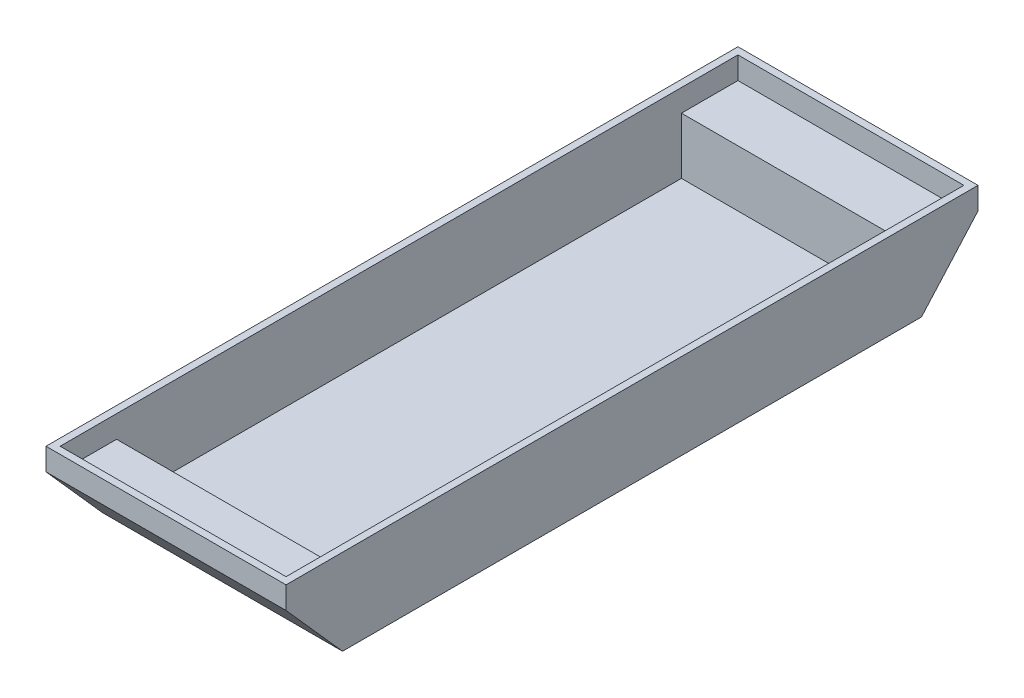
SolidWorks part; units mm, degrees
material "ABS PC"
ref_plane "Front Plane" through (0, 0, 0) normal (0, 0, 1) x (1, 0, 0)
ref_plane "Top Plane" through (0, 0, 0) normal (0, 1, 0) x (1, 0, 0)
ref_plane "Right Plane" through (0, 0, 0) normal (1, 0, 0) x (0, 0, -1)
sketch "Sketch3" plane through (0, 0, 0) normal (1, 0, 0) x (0, 0, -1)
  line L29 (108.2745, 46.8041) -> (95.5745, 32.5166)
  line L30 (108.2745, 46.8041) -> (95.5745, 46.8041)
  line L31 (-47.3005, 46.8041) -> (-34.6005, 32.5166)
  line L32 (-47.3005, 46.8041) -> (-34.6005, 46.8041)
  line L95 (95.5745, 32.5166) -> (95.5745, 46.8041)
  line L96 (68.587, 32.5166) -> (95.5745, 32.5166)
  line L97 (43.187, 32.5166) -> (68.587, 32.5166)
  line L98 (17.787, 32.5166) -> (43.187, 32.5166)
  line L99 (-7.613, 32.5166) -> (17.787, 32.5166)
  line L100 (-34.6005, 32.5166) -> (-7.613, 32.5166)
  line L101 (-34.6005, 46.8041) -> (-34.6005, 32.5166)
  line L102 (95.5745, 32.5166) -> (95.5745, 46.8041)
  line L103 (68.587, 32.5166) -> (95.5745, 32.5166)
  line L104 (43.187, 32.5166) -> (68.587, 32.5166)
  line L105 (17.787, 32.5166) -> (43.187, 32.5166)
  line L106 (-7.613, 32.5166) -> (17.787, 32.5166)
  line L107 (-34.6005, 32.5166) -> (-7.613, 32.5166)
  line L108 (-34.6005, 46.8041) -> (-34.6005, 32.5166)
  line L148 (-34.6005, 46.8041) -> (-33.013, 46.8041)
  line L149 (93.987, 46.8041) -> (95.5745, 46.8041)
  line L155 (93.987, 34.1041) -> (93.987, 46.8041)
  line L156 (68.587, 34.1041) -> (93.987, 34.1041)
  line L157 (43.187, 34.1041) -> (68.587, 34.1041)
  line L158 (17.787, 34.1041) -> (43.187, 34.1041)
  line L159 (-7.613, 34.1041) -> (17.787, 34.1041)
  line L160 (-33.013, 34.1041) -> (-7.613, 34.1041)
  line L161 (-33.013, 46.8041) -> (-33.013, 34.1041)
  line L162 (93.987, 34.1041) -> (93.987, 46.8041)
  line L163 (68.587, 34.1041) -> (93.987, 34.1041)
  line L164 (43.187, 34.1041) -> (68.587, 34.1041)
  line L165 (17.787, 34.1041) -> (43.187, 34.1041)
  line L166 (-7.613, 34.1041) -> (17.787, 34.1041)
  line L167 (-33.013, 34.1041) -> (-7.613, 34.1041)
  line L168 (-33.013, 46.8041) -> (-33.013, 34.1041)
  line L178 (106.687, 51.8041) -> (106.687, 46.8041) construction
  line L179 (-45.713, 51.8041) -> (-45.713, 46.8041) construction
  line L180 (-47.3005, 46.8041) -> (-47.3005, 51.8041)
  line L181 (-47.3005, 51.8041) -> (-45.713, 51.8041)
  line L182 (-45.713, 51.8041) -> (-45.713, 46.8041)
  line L183 (108.2745, 46.8041) -> (108.2745, 51.8041)
  line L184 (108.2745, 51.8041) -> (106.687, 51.8041)
  line L185 (106.687, 51.8041) -> (106.687, 46.8041)
  dimension "D3" = 1.5875
  dimension "D4" = 1.5875
  dimension "D1" = 1.5875
  dimension "D2" = 0
extrude "Boss-Extrude1" add sketch "Sketch3" along normal mid plane 53.975 contours L108 L32 L31 | L108 L107 L106 L105 L104 L103 L102 | L102 L29 L30 | L182 L181 L180 L32 | L184 L185 L30 L183 region at (0, 42.0416, -99.8078) region at (0, 49.3041, -107.4807) region at (0, 33.8262, -82.0807) region at (0, 42.0416, 38.8339) region at (0, 49.3041, 46.5068)
sketch "Sketch4" plane through (26.9875, 0, 0) normal (1, 0, 0) x (0, 0, -1)
  line L65 (93.987, 34.1041) -> (93.987, 46.8041) construction
  line L66 (-33.013, 46.8041) -> (-33.013, 34.1041) construction
  line L67 (-33.013, 34.1041) -> (93.987, 34.1041) construction
  line L68 (-45.713, 51.8041) -> (106.687, 51.8041) construction
  line L73 (-33.013, 46.8041) -> (-33.013, 34.1041)
  line L74 (-47.3005, 46.8041) -> (-33.013, 46.8041)
  line L75 (-33.013, 34.1041) -> (93.987, 34.1041)
  line L76 (93.987, 34.1041) -> (93.987, 46.8041)
  line L77 (93.987, 46.8041) -> (108.2745, 46.8041)
  line L78 (108.2745, 46.8041) -> (108.2745, 51.8041)
  line L79 (108.2745, 51.8041) -> (-47.3005, 51.8041)
  line L80 (-47.3005, 51.8041) -> (-47.3005, 46.8041)
extrude "Boss-Extrude2" add sketch "Sketch4" against normal blind 1.5875
mirror "Mirror1" about plane through (0, 0, 0) normal (1, 0, 0) of "Boss-Extrude2"
sketch "Sketch6" plane through (0, 32.5166, 0) normal (0, -1, 0) x (1, 0, 0)
  line L12 (26.9875, 34.6005) -> (-26.9875, 34.6005) construction
  line L13 (-23.8125, 31.4255) -> (23.8125, 31.4255)
  line L186 (-23.8125, 31.4255) -> (-23.8125, -92.3995)
  line L188 (-23.8125, -92.3995) -> (23.8125, -92.3995)
  line L190 (23.8125, 31.4255) -> (23.8125, -92.3995)
  line L194 (26.9875, 34.6005) -> (26.9875, -95.5745) construction
  line L196 (26.9875, -95.5745) -> (-26.9875, -95.5745) construction
  line L198 (-26.9875, 34.6005) -> (-26.9875, -95.5745) construction
  dimension "D1" = 3.175
  dimension "D2" = 3.175
  dimension "D3" = 3.175
  dimension "D4" = 3.175
extrude "Cut-Extrude1" [suppressed] cut sketch "Sketch6" against normal through all both and the other way through all contours L186 L13 L190 L188
sketch "Sketch7" plane through (0, 0, 0) normal (0, 1, 0) x (1, 0, 0)
  line L0 (25.4, -45.713) -> (-25.4, -45.713) construction
  line L1 (-25.4, 106.687) -> (-25.4, -45.713) construction
  line L2 (25.4, 106.687) -> (25.4, -45.713) construction
  circle A0 centre (-12.7, 100.337) radius 2.4638
  circle A1 centre (12.7, 100.337) radius 2.4638
  circle A2 centre (12.7, -39.363) radius 2.4638
  circle A3 centre (-12.7, -39.363) radius 2.4638
  dimension "D1" = 4.9276
  dimension "D3" = 139.7
  dimension "D4" = 25.4
  dimension "D5" = 6.35
  dimension "D6" = 12.7
  dimension "D7" = 12.7
  dimension "D8" = 139.7
  dimension "D9" = 139.7
  dimension "D2" = 25.4
extrude "Cut-Extrude2" [suppressed] cut sketch "Sketch7" against normal through all both and the other way through all
fillet "Fillet1" [suppressed] radius 19.05
fillet "Fillet2" [suppressed] radius 1.5875
fillet "Fillet4" [suppressed] radius 1.5875
